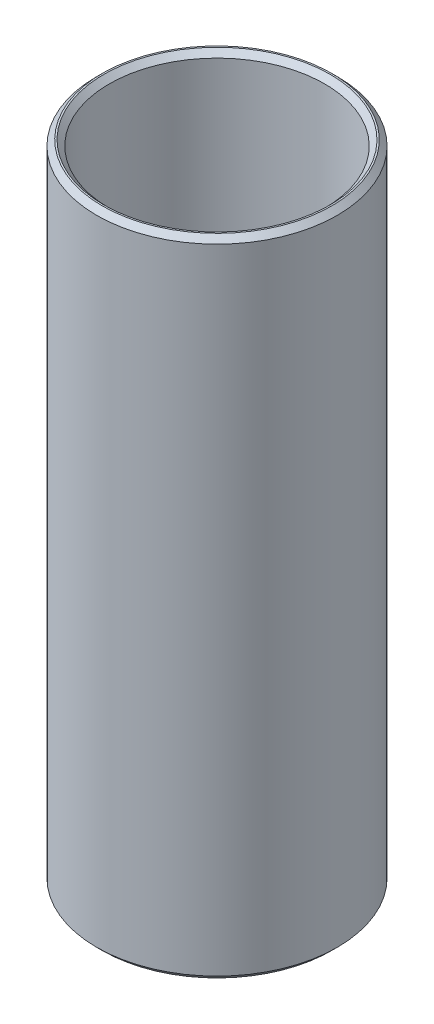
SolidWorks part; units mm, degrees
ref_plane "Front Plane" through (0, 0, 0) normal (0, 0, 1) x (1, 0, 0)
ref_plane "Top Plane" through (0, 0, 0) normal (0, 1, 0) x (1, 0, 0)
ref_plane "Right Plane" through (0, 0, 0) normal (1, 0, 0) x (0, 0, -1)
sketch "Sketch1" plane through (0, 0, 0) normal (0, 1, 0) x (1, 0, 0)
  circle A0 centre (0, 0) radius 35
  dimension "SLEEVE_OD" = 70
extrude "Boss-Extrude1" add sketch "Sketch1" along normal blind 187.6862
sketch "Sketch2" plane through (0, 0, 0) normal (0, 1, 0) x (1, 0, 0)
  circle A0 centre (0, 0) radius 31.3344
  dimension "BORE_D" = 62.6688
extrude "Cut-Extrude1" cut sketch "Sketch2" along normal through all
chamfer "Chamfer1" distance 1.5987 angle 45 4 edges at (0, 187.6862, 31.3344) (0, 0, 31.3344) (0, 0, 35) (0, 187.6862, 35)
